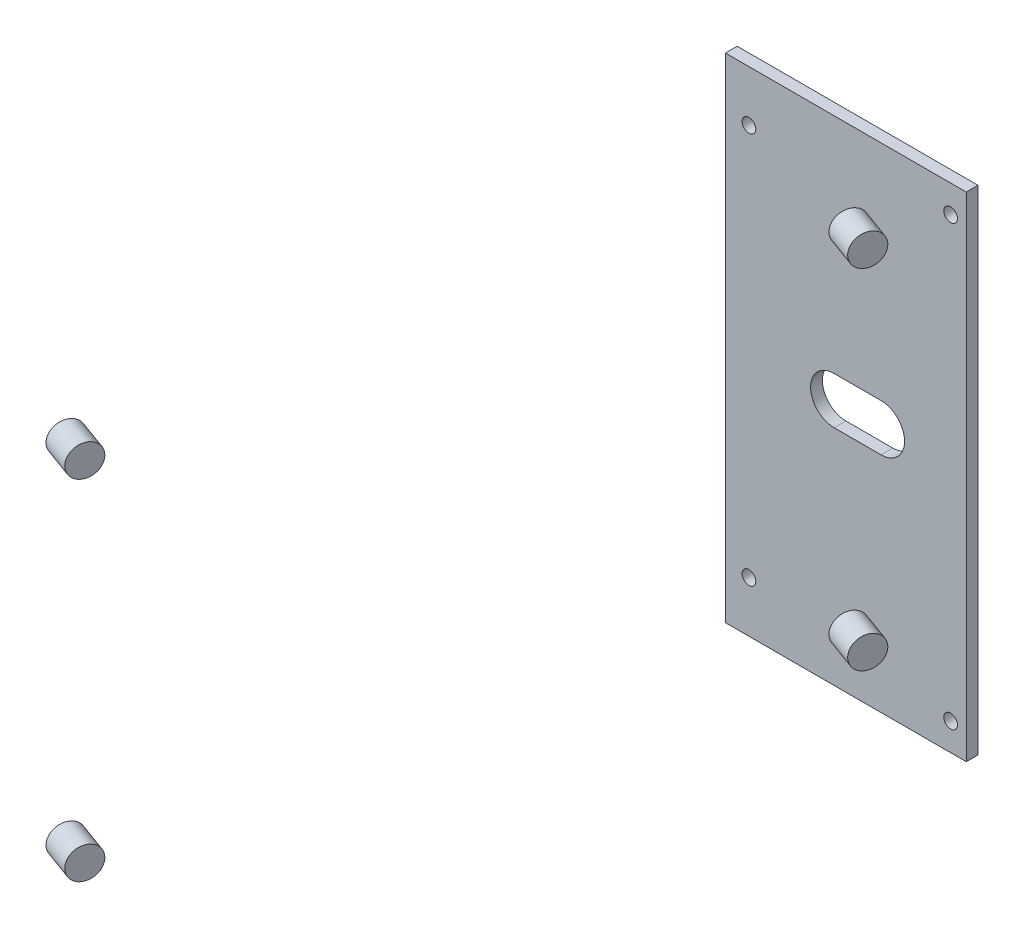
SolidWorks part; units mm, degrees
ref_plane "Front Plane" through (0, 0, 0) normal (0, 0, 1) x (1, 0, 0)
ref_plane "Top Plane" through (0, 0, 0) normal (0, 1, 0) x (1, 0, 0)
ref_plane "Right Plane" through (0, 0, 0) normal (1, 0, 0) x (0, 0, -1)
sketch "Sketch1" plane through (0, 0, 0) normal (0, 0, 1) x (1, 0, 0)
  line L0 (-83.8536, 0) -> (19.3888, 0) construction
  line L2 (-61.5, -63) -> (0, -63)
  line L3 (-61.5, -63) -> (-61.5, 63)
  line L4 (-61.5, 63) -> (0, 63)
  line L5 (0, -63) -> (0, 63)
  line L6 (-61.5, -63) -> (0, 63) construction
  line L7 (-61.5, 63) -> (0, -63) construction
  circle A0 centre (-4, 56) radius 1.75
  circle A1 centre (-55.5, 50) radius 1.75
  circle A2 centre (-4, -56) radius 1.75
  circle A3 centre (-55.5, -50) radius 1.75
  point P7 (-30.75, 0)
  dimension "D1" = 3.5
  dimension "D2" = 112
  dimension "D3" = 4
  dimension "D4" = 126
  dimension "D5" = 51.5
  dimension "D6" = 100
  dimension "D7" = 6
extrude "Boss-Extrude1" add sketch "Sketch1" along normal blind 3
sketch "Sketch2" plane through (0, 0, 3) normal (0, 0, 1) x (1, 0, 0)
  line L0 (-55.5, -50) -> (0, -50) construction
  line L1 (0, -63) -> (0, 63) construction
  line L2 (-27.75, -50) -> (-27.75, 63) construction
  line L3 (0, 63) -> (-61.5, 63) construction
  line L4 (0, 0) -> (-61.5, 0) construction
  line L5 (-61.5, 63) -> (-61.5, -63) construction
  line L6 (-33.75, 0) -> (-21.75, 0) construction
  line L7 (-33.75, 6) -> (-21.75, 6)
  line L8 (-33.75, -6) -> (-21.75, -6)
  arc A0 (-33.75, 6) -> (-33.75, -6) centre (-33.75, 0) ccw
  arc A1 (-21.75, -6) -> (-21.75, 6) centre (-21.75, 0) ccw
  point P16 (-27.75, 0)
  dimension "D1" = 12
  dimension "D2" = 12
extrude "Cut-Extrude1" cut sketch "Sketch2" against normal up to next
sketch "Sketch3" plane through (-13.0182, 0, -4.7382) normal (-0.9397, 0, -0.342) x (-0.342, 0, 0.9397)
  circle A0 centre (171.5115, 44.5) radius 4
  circle A1 centre (171.5115, -44.5) radius 4
  circle A2 centre (15.5115, -44.5) radius 4
  circle A3 centre (15.5115, 44.5) radius 4
  dimension "D1" = 8
extrude "Boss-Extrude2" add sketch "Sketch3" along normal blind 8 separate body
